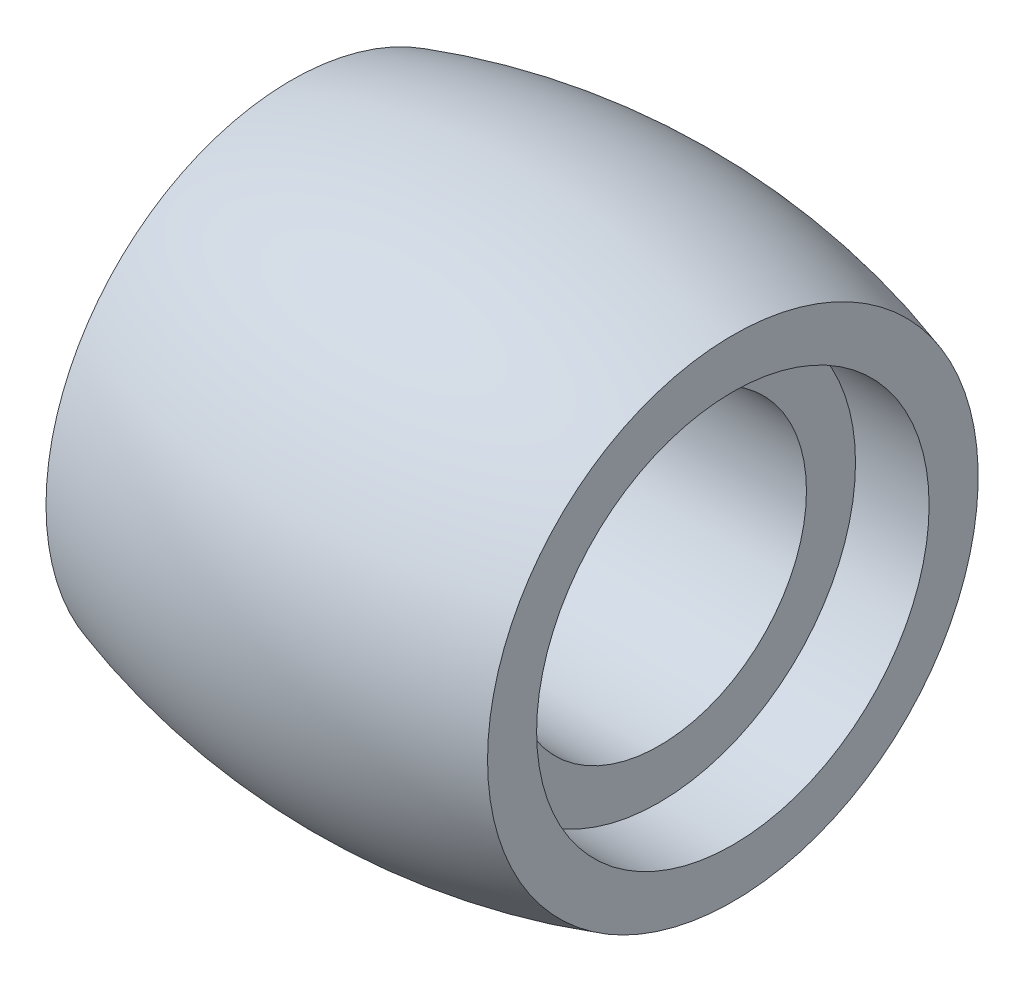
SolidWorks part; units mm, degrees
ref_plane "Front Plane" through (0, 0, 0) normal (0, 0, 1) x (1, 0, 0)
ref_plane "Top Plane" through (0, 0, 0) normal (0, 1, 0) x (1, 0, 0)
ref_plane "Right Plane" through (0, 0, 0) normal (1, 0, 0) x (0, 0, -1)
sketch "Sketch2" plane through (0, 0, 0) normal (0, 0, 1) x (1, 0, 0)
  line L0 (0, 6.5859) -> (0, -8.2148) construction
  line L1 (-8.918, 0) -> (11.5313, 0) construction
  line L2 (-3, 3) -> (3, 3)
  line L3 (3, 3) -> (3, 4)
  line L4 (3, 4) -> (4.5, 4)
  line L5 (4.5, 4) -> (4.5, 5)
  line L6 (-4.5, 4) -> (-4.5, 5)
  line L7 (-3, 4) -> (-4.5, 4)
  line L8 (-3, 3) -> (-3, 4)
  arc A0 (-4.5, 5) -> (4.5, 5) centre (0, -9.3091) cw
  point P18 (0, 3)
  dimension "D6" = 15
  dimension "1.5" = 3
  dimension "D2" = 1.5
  dimension "2.9" = 4
  dimension "D4" = 5
  dimension "D5" = 4.5
revolve "Revolve1" add sketch "Sketch2" angle 360 about L1
